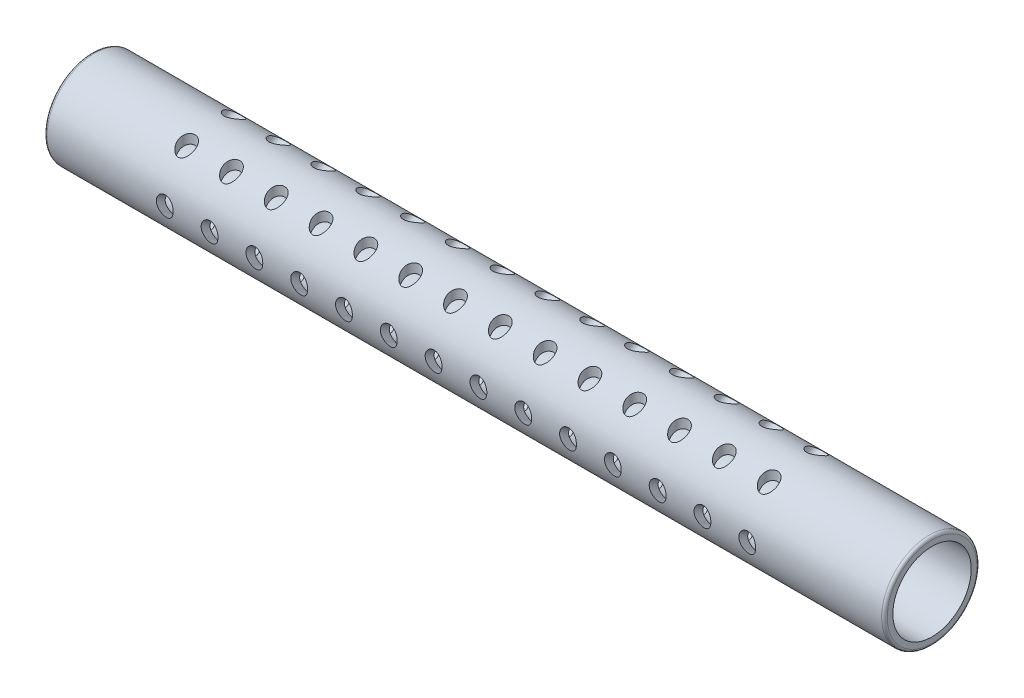
SolidWorks part; units mm, degrees
ref_plane "Front Plane" through (0, 0, 0) normal (0, 0, 1) x (1, 0, 0)
ref_plane "Top Plane" through (0, 0, 0) normal (0, 1, 0) x (1, 0, 0)
ref_plane "Right Plane" through (0, 0, 0) normal (1, 0, 0) x (0, 0, -1)
sketch "Sketch1" plane through (0, 0, 0) normal (1, 0, 0) x (0, 0, -1)
  circle A0 centre (0, 0) radius 8.5
  circle A1 centre (0, 0) radius 7
  dimension "D1" = 17
  dimension "D2" = 14
extrude "Boss-Extrude1" add sketch "Sketch1" along normal mid plane 150
sketch "Sketch2" plane through (0, 0, 0) normal (0, 1, 0) x (1, 0, 0)
  line L0 (-75, 4.5784) -> (-55, 4.5784)
  line L1 (-75, 8.5) -> (-75, -8.5) construction
  circle A0 centre (-53.5, 4.5784) radius 1.5
  point P6 (0, 0)
  dimension "D1" = 20
  dimension "D2" = 1.5
extrude "Cut-Extrude2" cut sketch "Sketch2" against normal up to next contours A0 | A0 region at (-53.5, 0, -4.5784)
pattern_linear "LPattern1" count 14 spacing 8 along (1, 0, 0) of "Cut-Extrude2"
pattern_circular "CirPattern1" count 6 over 360 about axis through (75, 0, 0) along (-1, 0, 0) of "LPattern1"
fillet "Fillet1" radius 0.5 2 edges at (-75, 0, -8.5) (75, 0, -8.5)
